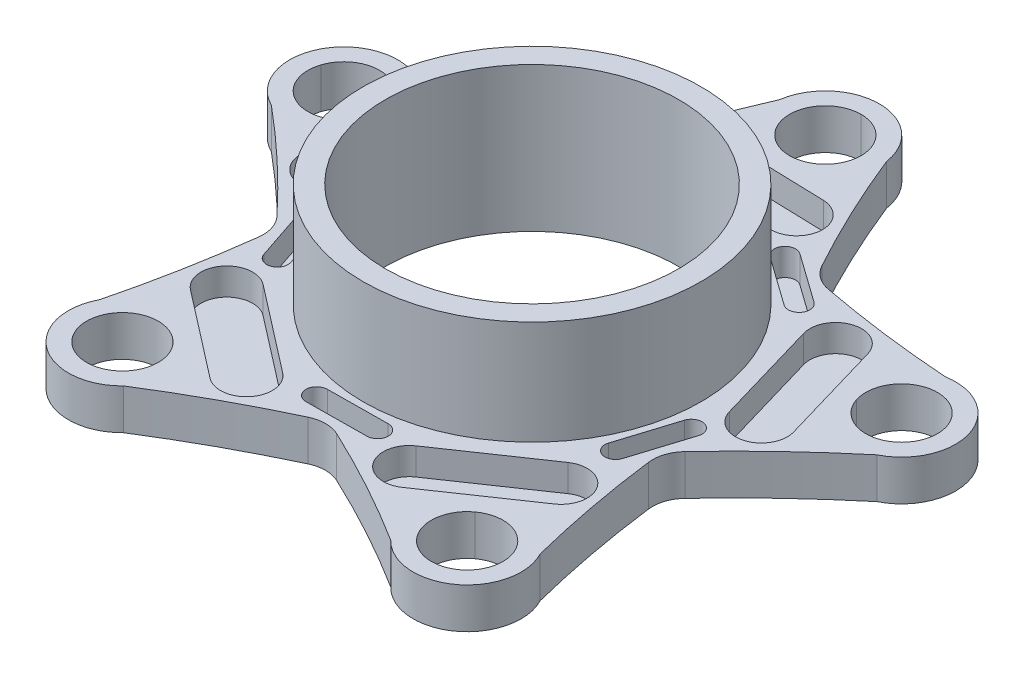
SolidWorks part; units mm, degrees
note: '?' marks a value the reader was unsure of.
ref_plane "Front Plane" through (0, 0, 0) normal (0, 0, 1) x (1, 0, 0)
ref_plane "Top Plane" through (0, 0, 0) normal (0, 1, 0) x (1, 0, 0)
ref_plane "Right Plane" through (0, 0, 0) normal (1, 0, 0) x (0, 0, -1)
sketch "Sketch1" plane through (0, 0, 0) normal (0, 1, 0) x (1, 0, 0)
  circle A0 centre (0, 0) radius 31.75
  dimension "D1" = 63.5
extrude "CenterCircleExtrude" add sketch "Sketch1" along normal blind 19.558 contours A0
sketch "Sketch2" plane through (0, 0, 0) normal (0, -1, 0) x (1, 0, 0)
  circle A0 centre (0, 0) radius 80.01
  dimension "D1" = 160.02
extrude "BaseExpand" add sketch "Sketch2" along normal blind 7.62
sketch "Sketch3" plane through (0, 19.558, 0) normal (0, 1, 0) x (1, 0, 0)
  circle A0 centre (0, 0) radius 27.559
  dimension "D1" = 55.118
extrude "CenterCut" cut sketch "Sketch3" against normal blind 27.178 contours A0
sketch "Sketch4" plane through (0, 0, 0) normal (0, 1, 0) x (1, 0, 0)
  line L0 (-52.4203, 17.0324) -> (0, 55.118) construction
  line L1 (-26.2102, 36.0752) -> (-18.6622, 25.6863) construction
  circle A0 centre (0, 55.118) radius 6.731
  circle A1 centre (52.4203, 17.0324) radius 6.731
  circle A2 centre (32.3975, -44.5914) radius 6.731
  circle A3 centre (-32.3975, -44.5914) radius 6.731
  circle A4 centre (-52.4203, 17.0324) radius 6.731
  circle A5 centre (0, 0) radius 31.75 construction
  point P14 (0, 0)
  dimension "D1" = 13.462
  dimension "D2" = 55.118
  dimension "D3" = 5
extrude "OuterCircleCut" cut sketch "Sketch4" against normal blind 7.62
sketch "Sketch8" plane through (0, 0, 0) normal (0, 1, 0) x (1, 0, 0)
  line L0 (-52.4203, 17.0324) -> (0, 55.118) construction
  line L1 (-26.2102, 36.0752) -> (-18.6622, 25.6863) construction
  line L2 (26.2102, 36.0752) -> (18.6622, 25.6863) construction
  line L3 (42.4089, -13.7795) -> (30.196, -9.8113) construction
  line L4 (0, -44.5914) -> (0, -31.75) construction
  line L5 (-42.4089, -13.7795) -> (-30.196, -9.8113) construction
  line L6 (0, -14.9479) -> (0, 14.9479) construction
  line L8 (0, 0) -> (10.16, 55.118) construction
  line L9 (10.16, 55.118) -> (-10.16, 55.118) construction
  circle A0 centre (-52.4203, 17.0324) radius 10.16
  circle A1 centre (0, 55.118) radius 10.16
  circle A2 centre (52.4203, 17.0324) radius 10.16
  circle A3 centre (32.3975, -44.5914) radius 10.16
  circle A4 centre (-32.3975, -44.5914) radius 10.16
  circle A5 centre (0, 0) radius 31.75 construction
  arc A6 (22.4362, 30.8807) -> (8.4002, 60.8331) centre (204.9622, 134.6791) cw
  arc A7 (-22.4362, 30.8807) -> (-8.4002, 60.8331) centre (-204.9622, 134.6791) ccw
  arc A8 (22.4362, 30.8807) -> (55.2599, 26.7875) centre (64.7506, 236.5488) ccw
  arc A9 (36.3025, -11.7954) -> (60.4515, 10.8094) centre (191.4243, -153.3125) cw
  arc A10 (36.3025, -11.7954) -> (42.5527, -44.2774) centre (244.9803, 11.5161) ccw
  arc A11 (0, -38.1707) -> (28.9609, -54.1525) centre (-86.6555, -229.4315) cw
  arc A12 (0, -38.1707) -> (-28.9609, -54.1525) centre (86.6555, -229.4315) ccw
  arc A13 (-36.3025, -11.7954) -> (-42.5527, -44.2774) centre (-244.9803, 11.5161) cw
  arc A14 (-36.3025, -11.7954) -> (-60.4515, 10.8094) centre (-191.4243, -153.3125) ccw
  arc A15 (-22.4362, 30.8807) -> (-55.2599, 26.7875) centre (-64.7506, 236.5488) cw
  point P14 (0, 0)
  point P27 (0, 0)
  point P63 (0, 0)
  point P72 (0, 0)
  dimension "D1" = 5
  dimension "D3" = 5
  dimension "D2" = 5
extrude "StarfishCut" cut sketch "Sketch8" against normal blind 7.62
sketch "Sketch14" plane through (0, 0, 0) normal (0, 1, 0) x (1, 0, 0)
  line L0 (-35.0288, -5.7028) -> (-31.4189, -16.4524) construction
  line L4 (-31.5013, -25.8769) -> (-15.2419, -38.4471) construction
  line L6 (-33.12, -5.0618) -> (-29.5101, -15.8114)
  line L7 (-36.9376, -6.3438) -> (-33.3277, -17.0934)
  line L8 (-16.2482, 31.5521) -> (-25.3562, 24.7971) construction
  line L9 (-15.0487, 29.9349) -> (-24.1567, 23.1798)
  line L10 (-17.4477, 33.1694) -> (-26.5556, 26.4144)
  line L11 (24.9869, 25.2031) -> (15.748, 31.7779) construction
  line L12 (23.8194, 23.5625) -> (14.5805, 30.1373)
  line L13 (26.1544, 26.8436) -> (16.9154, 33.4184)
  line L14 (31.6909, -15.9758) -> (35.0889, -5.1573) construction
  line L15 (29.7699, -15.3724) -> (33.1679, -4.5539)
  line L16 (33.612, -16.5792) -> (37.01, -5.7607)
  line L17 (-5.4008, -35.0767) -> (5.9382, -34.9653) construction
  line L18 (-5.4206, -33.0632) -> (5.9184, -32.9518)
  line L19 (-5.3811, -37.0901) -> (5.958, -36.9787)
  line L20 (-28.5253, -22.0275) -> (-12.2659, -34.5977)
  line L23 (-34.4773, -29.7263) -> (-18.2178, -42.2965)
  line L24 (-34.3448, 21.9631) -> (-41.2754, 2.6151) construction
  line L25 (-29.7642, 20.3223) -> (-36.6948, 0.9743)
  line L26 (-38.9254, 23.6039) -> (-45.856, 4.2558)
  line L27 (10.275, 39.4508) -> (-10.2677, 40.0633) construction
  line L28 (10.13, 34.5874) -> (-10.4127, 35.1999)
  line L29 (10.42, 44.3143) -> (-10.1227, 44.9268)
  line L30 (40.6951, 2.4188) -> (34.9296, 22.1454) construction
  line L31 (36.0249, 1.0539) -> (30.2593, 20.7805)
  line L32 (45.3654, 3.7838) -> (39.5998, 23.5104)
  line L33 (14.8759, -37.9559) -> (31.8554, -26.3767) construction
  line L34 (12.1346, -33.9361) -> (29.114, -22.3568)
  line L35 (17.6173, -41.9757) -> (34.5967, -30.3965)
  arc A43 (-33.12, -5.0618) -> (-36.9376, -6.3438) centre (-35.0288, -5.7028) ccw
  arc A44 (-33.3277, -17.0934) -> (-29.5101, -15.8114) centre (-31.4189, -16.4524) ccw
  arc A64 (-15.0487, 29.9349) -> (-17.4477, 33.1694) centre (-16.2482, 31.5521) ccw
  arc A65 (-26.5556, 26.4144) -> (-24.1567, 23.1798) centre (-25.3562, 24.7971) ccw
  arc A66 (23.8194, 23.5625) -> (26.1544, 26.8436) centre (24.9869, 25.2031) ccw
  arc A67 (16.9154, 33.4184) -> (14.5805, 30.1373) centre (15.748, 31.7779) ccw
  arc A68 (29.7699, -15.3724) -> (33.612, -16.5792) centre (31.6909, -15.9758) ccw
  arc A69 (37.01, -5.7607) -> (33.1679, -4.5539) centre (35.0889, -5.1573) ccw
  arc A70 (-5.4206, -33.0632) -> (-5.3811, -37.0901) centre (-5.4008, -35.0767) ccw
  arc A71 (5.958, -36.9787) -> (5.9184, -32.9518) centre (5.9382, -34.9653) ccw
  arc A74 (-28.5253, -22.0275) -> (-34.4773, -29.7263) centre (-31.5013, -25.8769) ccw
  arc A75 (-18.2178, -42.2965) -> (-12.2659, -34.5977) centre (-15.2419, -38.4471) ccw
  arc A76 (-29.7642, 20.3223) -> (-38.9254, 23.6039) centre (-34.3448, 21.9631) ccw
  arc A77 (-45.856, 4.2558) -> (-36.6948, 0.9743) centre (-41.2754, 2.6151) ccw
  arc A78 (10.13, 34.5874) -> (10.42, 44.3143) centre (10.275, 39.4508) ccw
  arc A79 (-10.1227, 44.9268) -> (-10.4127, 35.1999) centre (-10.2677, 40.0633) ccw
  arc A80 (36.0249, 1.0539) -> (45.3654, 3.7838) centre (40.6951, 2.4188) ccw
  arc A81 (39.5998, 23.5104) -> (30.2593, 20.7805) centre (34.9296, 22.1454) ccw
  arc A82 (12.1346, -33.9361) -> (17.6173, -41.9757) centre (14.8759, -37.9559) ccw
  arc A83 (34.5967, -30.3965) -> (29.114, -22.3568) centre (31.8554, -26.3767) ccw
  point P2 (-33.2239, -11.0776)
  point P5 (-23.3716, -32.162)
  point P15 (-37.8101, 12.2891)
  point P22 (0.0037, 39.7571)
  point P29 (37.8123, 12.2821)
  point P34 (0, 0)
  point P37 (23.3657, -32.1663)
  point P42 (0, 0)
  point P51 (0.0346, -0.0647)
  point P61 (0, 0)
  point P67 (-20.8022, 28.1746)
  point P74 (20.3674, 28.4905)
  point P81 (33.3899, -10.5665)
  point P88 (0.2687, -35.021)
  point P93 (0, 0)
  point P97 (0, 0)
  dimension "D1" = 5
  dimension "D5" = 5
extrude "Batman Cut" cut sketch "Sketch14" against normal blind 5.08
ref_axis "Axis1" through (0, -7.62, 0) along (0, 1, 0)?
fillet "Fillet12" radius 6.35 5 edges at (-36.3025, -3.81, 11.7954) (0, -3.81, 38.1707) (36.3025, -3.81, 11.7954) (22.4362, -3.81, -30.8807) (-22.4362, -3.81, -30.8807)
ref_plane "Plane1" through (0, 0, 0) normal (-0.309, 0, 0.9511) x (0.9511, 0, 0.309)
ref_plane "Plane2" through (0, 0, 0) normal (-0.809, 0, -0.5878) x (-0.5878, 0, 0.809)
ref_plane "Plane3" through (0, 0, 0) normal (-0.809, 0, 0.5878) x (0.5878, 0, 0.809)
ref_plane "Plane4" through (0, 0, 0) normal (0.309, 0, 0.9511) x (0.9511, 0, -0.309)
split line "Split Line1"
split line "Split Line2"
split line "Split Line3"
split line "Split Line4"
split line "Split Line5"
